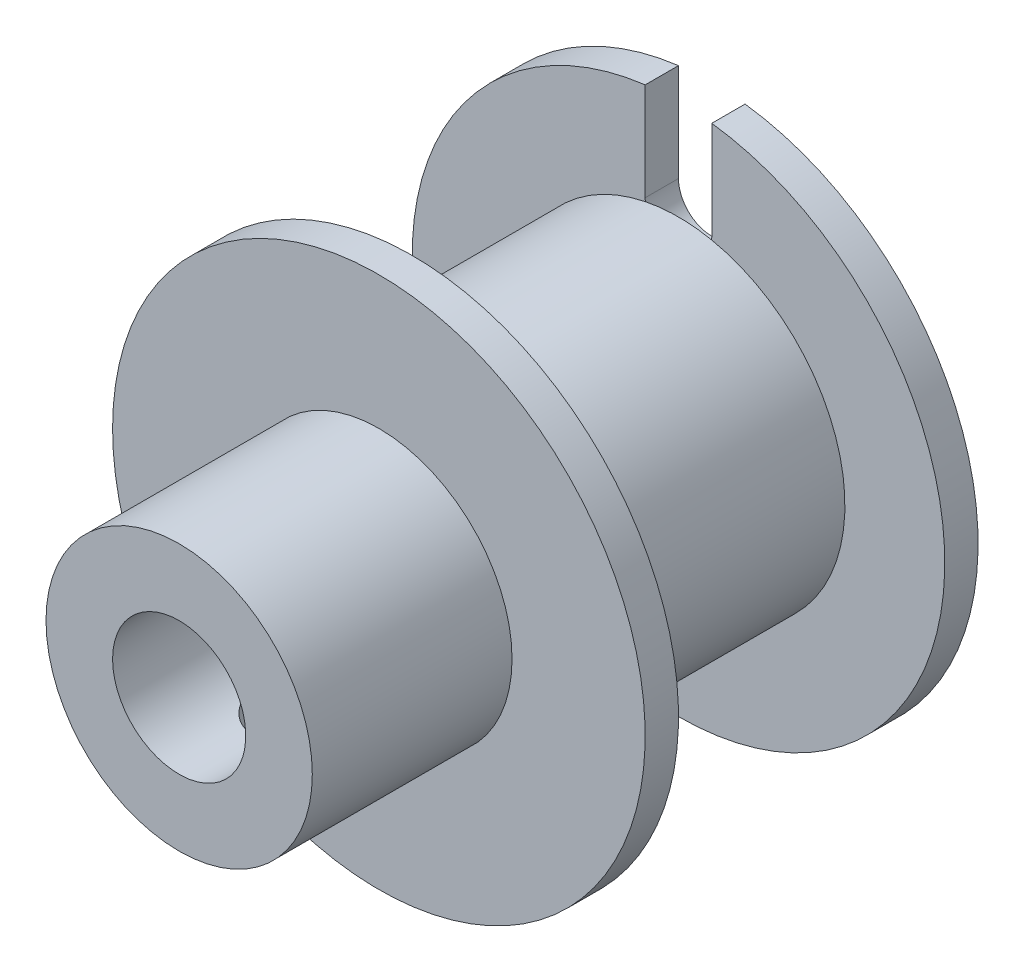
SolidWorks part; units mm, degrees
ref_plane "Front Plane" through (0, 0, 0) normal (0, 0, 1) x (1, 0, 0)
ref_plane "Top Plane" through (0, 0, 0) normal (0, 1, 0) x (1, 0, 0)
ref_plane "Right Plane" through (0, 0, 0) normal (1, 0, 0) x (0, 0, -1)
sketch "Sketch1" plane through (15.3043, 0, 0) normal (1, 0, 0) x (0, 0, -1)
  line L0 (93.4456, 24.7035) -> (-13.843, 24.7035) construction
  line L1 (58.1078, 37.4035) -> (58.1078, 12.0035) construction
  line L2 (59.6953, 37.4035) -> (58.1078, 37.4035) construction
  line L3 (59.6953, 37.4035) -> (59.6953, 12.0035) construction
  line L4 (59.6953, 32.641) -> (72.3953, 32.641) construction
  line L5 (72.3953, 37.4035) -> (72.3953, 12.0035) construction
  line L6 (72.3953, 37.4035) -> (73.9828, 37.4035) construction
  line L7 (73.9828, 37.4035) -> (73.9828, 12.0035) construction
  line L8 (22.225, 24.7035) -> (9.525, 24.7035)
  line L9 (58.1078, 37.4035) -> (58.1078, 31.0535)
  line L10 (59.6953, 37.4035) -> (58.1078, 37.4035)
  line L11 (59.6953, 37.4035) -> (59.6953, 32.641)
  line L12 (59.6953, 32.641) -> (72.3953, 32.641)
  line L13 (72.3953, 37.4035) -> (72.3953, 32.641)
  line L14 (72.3953, 37.4035) -> (73.9828, 37.4035)
  line L15 (73.9828, 37.4035) -> (73.9828, 27.8785)
  line L16 (93.4456, 27.8785) -> (-1.5875, 27.8785) construction
  line L17 (93.4456, 27.8785) -> (48.5828, 27.8785)
  line L18 (58.1078, 31.0535) -> (48.5828, 31.0535) construction
  line L19 (48.5828, 18.3535) -> (48.5828, 31.0535) construction
  line L21 (58.1078, 37.4035) -> (58.1078, 31.0535)
  line L22 (58.1078, 31.0535) -> (48.5828, 31.0535)
  line L23 (48.5828, 27.8785) -> (48.5828, 31.0535)
revolve "Revolve1" add sketch "Sketch1" angle 360 about L8 region at (15.3043, 30.6566, -62.8703)
sketch "Sketch2" plane through (0, 0, -73.9828) normal (0, 0, -1) x (-1, 0, 0)
  line L0 (-15.3043, 37.4035) -> (-15.3043, 12.0035) construction
  line L1 (-15.3043, 37.4035) -> (-15.3043, 12.0035)
  line L2 (-15.3043, 37.4035) -> (-15.3043, 32.641) construction
  line L3 (-13.7168, 37.4035) -> (-13.7168, 32.641)
  line L4 (-16.8918, 37.4035) -> (-16.8918, 32.641)
  arc A0 (-13.7168, 37.4035) -> (-16.8918, 37.4035) centre (-15.3043, 37.4035) ccw
  arc A1 (-16.8918, 32.641) -> (-13.7168, 32.641) centre (-15.3043, 32.641) ccw
  point P2 (-15.3043, 35.0222)
  circle M3 centre (-15.3043, 24.7035) radius 12.7
  dimension "D1" = 1.5875
  dimension "D2" = 4.7625
extrude "Cut-Extrude1" cut sketch "Sketch2" against normal up to surface (1.5875 mm away) contours L1 A1 L3 M3 | L4 A1 L1 M3 region at (14.5378, 34.3718, -73.9828) region at (16.0708, 34.3718, -73.9828) up to face at (7.3668, 24.7035, -72.3953)
ref_plane "Plane1" through (0, 18.3535, 0) normal (0, -1, 0) x (-1, 0, 0)
hole_wizard "#6-32 Tapped Hole1" positions "Sketch3" profile "Sketch4" tap size "#6-32" standard "ANSI Inch"
sketch "Sketch3" plane through (0, 18.3535, 0) normal (0, -1, 0) x (-1, 0, 0)
  line L0 (-15.3043, 58.1078) -> (-15.3043, 48.5828) construction
  point P0 (-15.3043, 53.3453)
sketch "Sketch4" plane through (15.3043, 18.3535, -53.3453) normal (1, 0, 0) x (0, 0, -1)
  line L0 (0, 0) -> (0, 7.1627)
  line L1 (0, 7.1627) -> (1.3525, 6.35)
  line L2 (1.3525, 6.35) -> (1.3525, 0)
  line L5 (1.3525, 0) -> (0, 0)
  line L10 (0, 7.1627) -> (-1.3526, 6.35) construction
  line L11 (0, -6.35) -> (0, 107.95) construction
  dimension "Tap Drill Dia." = 2.7051
  dimension "Tap Drill Depth" = 6.35
  dimension "Drill Angle" = 118
cosmetic thread "Hole Thread1" parameters "D1"=3.4775, "D2"=3.5052
